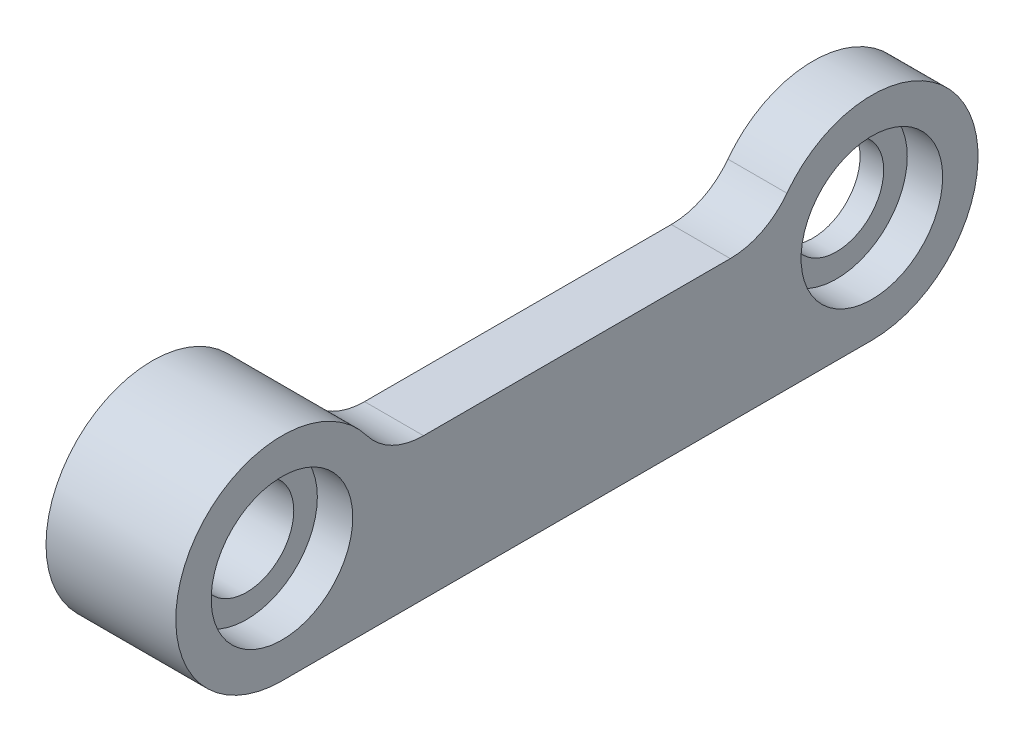
SolidWorks part; units mm, degrees
ref_plane "前视基准面" through (0, 0, 0) normal (0, 0, 1) x (1, 0, 0)
ref_plane "上视基准面" through (0, 0, 0) normal (0, 1, 0) x (1, 0, 0)
ref_plane "右视基准面" through (0, 0, 0) normal (1, 0, 0) x (0, 0, -1)
other "Configuration Table"
sketch "草图1" plane through (0, 0, 0) normal (1, 0, 0) x (0, 0, -1)
  line L1 (0, 0) -> (25, 0)
  line L2 (0, 0) -> (0, -6)
  line L3 (0, -6) -> (25, -6)
  line L4 (25, 0) -> (25, -6)
  circle A0 centre (0, -1.5) radius 4.5
  circle A1 centre (25, -1.5) radius 4.5
  circle A2 centre (0, -1.5) radius 2
  circle A3 centre (25, -1.5) radius 2
  dimension "D1" = 9
  dimension "D2" = 9
  dimension "D4" = 4
  dimension "D3" = 6
  dimension "D5" = 25
extrude "凸台-拉伸1" add sketch "草图1" along normal blind 2.5 contours A0 | L1 L4 L3 L2 | A1
extrude "凸台-拉伸3" add sketch "草图1<5>" against normal blind 3 contours A0
sketch "草图1<5>" plane through (0, 0, 0) normal (1, 0, 0) x (0, 0, -1) same geometry as "草图1"
extrude "切除-拉伸2" cut sketch "草图1<4>" along normal through all both and the other way through all contours L2 A2 | L2 A2 | L4 A3 L1 | L1 A3 L4 region at (0, -1.3854, 0.7577) region at (0, -1.6324, -0.8755) region at (0, -1.3854, -25.7577) region at (0, -1.6324, -24.1245)
sketch "草图1<4>" plane through (0, 0, 0) normal (1, 0, 0) x (0, 0, -1) same geometry as "草图1"
fillet "圆角1" radius 3 2 edges at (1.25, 0, -20.7574) (1.25, 0, -4.2426)
sketch "草图2" plane through (2.5, 0, 0) normal (1, 0, 0) x (0, 0, -1)
  circle A0 centre (0, -1.5) radius 3
  circle A1 centre (25, -1.5) radius 3
  dimension "D1" = 6
extrude "切除-拉伸3" cut sketch "草图2" against normal blind 1.5
ref_plane "基准面1" through (3.5, 0, 0) normal (1, 0, 0) x (0, 0, -1)
mirror "镜向2" about plane through (3.5, 0, 0) normal (1, 0, 0) of bodies 110
sketch "草图3" plane through (3.5, 0, 0) normal (1, 0, 0) x (0, 0, -1)
  line L1 (-8.2827, 6.9332) -> (33.6198, 6.9332)
  line L2 (-8.2827, 6.9332) -> (-8.2827, -10.198)
  line L3 (-8.2827, -10.198) -> (33.6198, -10.198)
  line L4 (33.6198, 6.9332) -> (33.6198, -10.198)
extrude "切除-拉伸4" cut sketch "草图3" along normal through all both
